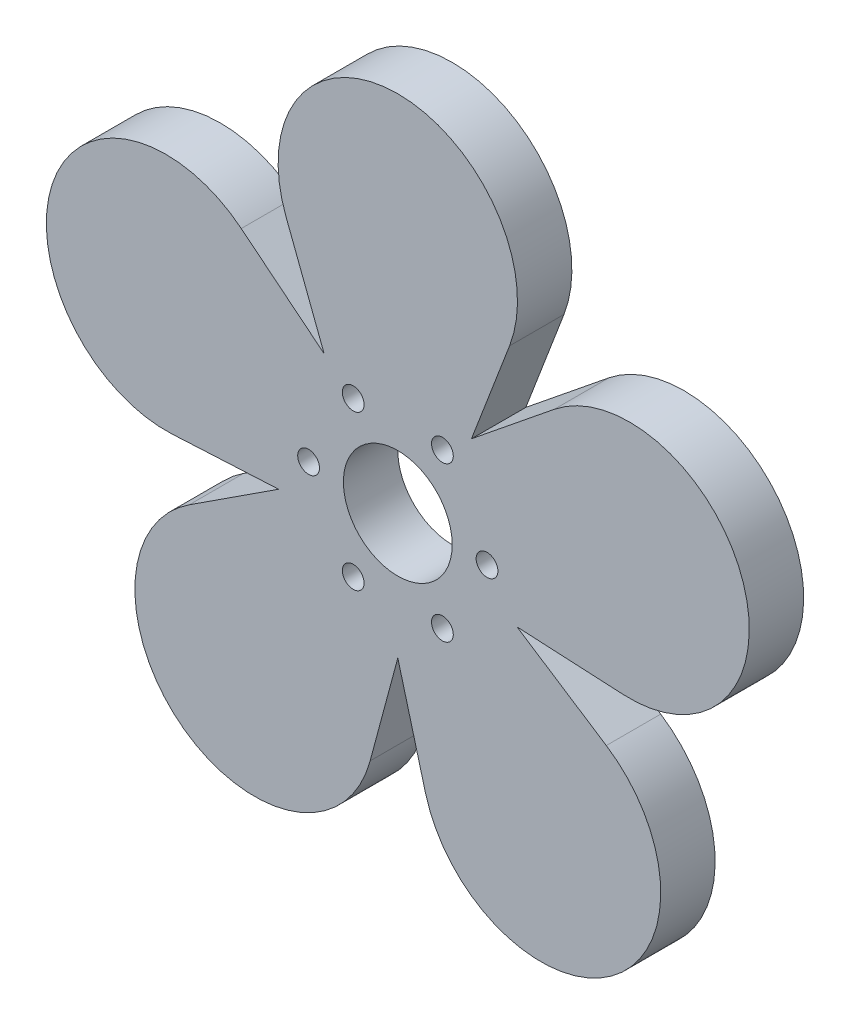
SolidWorks part; units mm, degrees
ref_plane "Piano frontale" through (0, 0, 0) normal (0, 0, 1) x (1, 0, 0)
ref_plane "Piano superiore" through (0, 0, 0) normal (0, 1, 0) x (1, 0, 0)
ref_plane "Piano destro" through (0, 0, 0) normal (1, 0, 0) x (0, 0, -1)
sketch "Schizzo1" plane through (0, 0, 0) normal (0, 0, 1) x (1, 0, 0)
  line L0 (0, 0) -> (0, 38.86) construction
  line L1 (-10.2726, 18.4664) -> (-6.769, 9.3168)
  line L2 (10.2726, 18.4664) -> (6.769, 9.3168)
  line L3 (14.3882, 15.4763) -> (6.769, 9.3168)
  line L4 (20.737, -4.0634) -> (10.9525, -3.5587)
  line L5 (19.165, -8.9015) -> (10.9525, -3.5587)
  line L6 (2.5435, -20.9777) -> (0, -11.5162)
  line L7 (-2.5435, -20.9777) -> (0, -11.5162)
  line L8 (-19.165, -8.9015) -> (-10.9525, -3.5587)
  line L9 (-20.737, -4.0634) -> (-10.9525, -3.5587)
  line L10 (-14.3882, 15.4763) -> (-6.769, 9.3168)
  circle A0 centre (0, 0) radius 11.4 construction
  circle A1 centre (0, 0) radius 5
  arc A2 (10.2726, 18.4664) -> (-10.2726, 18.4664) centre (0, 22.4) ccw
  arc A3 (20.737, -4.0634) -> (14.3882, 15.4763) centre (21.3037, 6.922) ccw
  arc A4 (2.5435, -20.9777) -> (19.165, -8.9015) centre (13.1664, -18.122) ccw
  arc A5 (-19.165, -8.9015) -> (-2.5435, -20.9777) centre (-13.1664, -18.122) ccw
  arc A6 (-14.3882, 15.4763) -> (-20.737, -4.0634) centre (-21.3037, 6.922) ccw
  point P6 (0, 0)
  point P33 (0, 0)
  dimension "D1" = 22.8
  dimension "D2" = 22
  dimension "D4" = 10
  dimension "D3" = 5
extrude "Estrusione-Estrusione1" add sketch "Schizzo1" along normal blind 5 contours L10 L1 A2 L2 L3 A3 L4 L5 A4 L6 L7 A5 L8 L9 A6
sketch "Schizzo2" plane through (0, 0, 5) normal (0, 0, 1) x (1, 0, 0)
  line L0 (5, 0) -> (11.4, 0) construction
  circle A0 centre (0, 0) radius 5 construction
  circle A1 centre (0, 0) radius 11.4 construction
  circle A2 centre (8.2, 0) radius 1
  circle A3 centre (4.1, -7.1014) radius 1
  circle A4 centre (-4.1, -7.1014) radius 1
  circle A5 centre (-8.2, 0) radius 1
  circle A6 centre (-4.1, 7.1014) radius 1
  circle A7 centre (4.1, 7.1014) radius 1
  point P21 (0, 0)
  point P22 (0.2893, 0.5011)
  dimension "D1" = 2
  dimension "D2" = 6
extrude "Taglio-Estrusione1" cut sketch "Schizzo2" against normal blind 5
sketch "Schizzo3" plane through (0, 0, 5) normal (0, 0, 1) x (1, 0, 0)
  circle A0 centre (0, 0) radius 5
  dimension "D1" = 10
extrude "Estrusione-Estrusione2" add sketch "Schizzo1<4>" along normal blind 5 contours A1
sketch "Schizzo1<4>" plane through (0, 0, 0) normal (0, 0, 1) x (1, 0, 0) same geometry as "Schizzo1"
extrude "Taglio-Estrusione2" cut sketch "Schizzo1<5>" along normal blind 5 contours A1
sketch "Schizzo1<5>" plane through (0, 0, 0) normal (0, 0, 1) x (1, 0, 0) same geometry as "Schizzo1"
